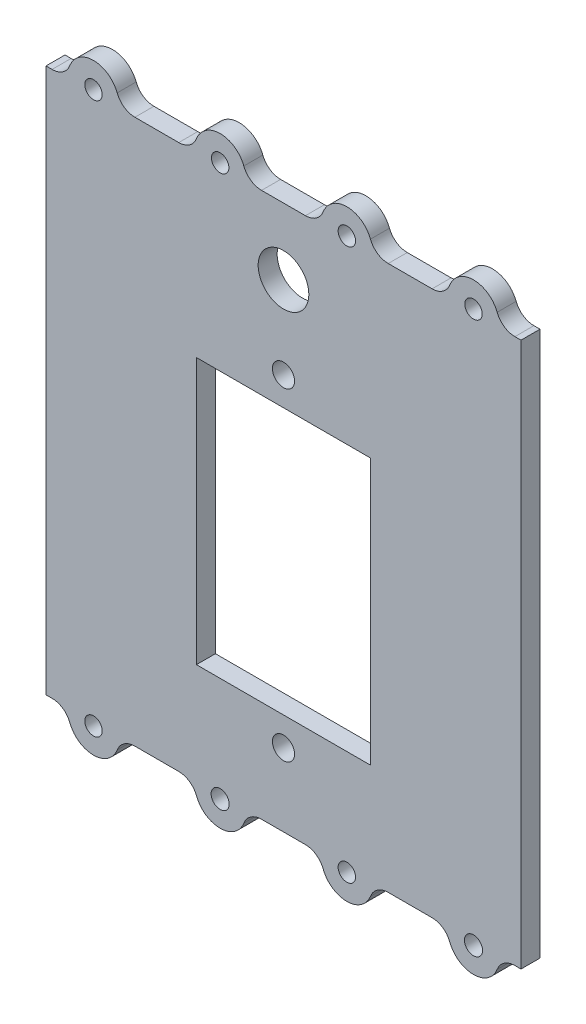
SolidWorks part; units mm, degrees
material "Aircraft Ply"
ref_plane "Front Plane" through (0, 0, 0) normal (0, 0, 1) x (1, 0, 0)
ref_plane "Top Plane" through (0, 0, 0) normal (0, 1, 0) x (1, 0, 0)
ref_plane "Right Plane" through (0, 0, 0) normal (1, 0, 0) x (0, 0, -1)
sketch "Sketch1" plane through (0, 0, 0) normal (0, 0, 1) x (1, 0, 0)
  line L13 (-3.4617, -43) -> (3.4617, -43)
  line L14 (16.5383, -43) -> (23.4617, -43)
  line L15 (36.5383, -43) -> (37.5, -43)
  line L16 (37.5, -43) -> (37.5, 43)
  line L17 (37.5, 43) -> (36.5383, 43)
  line L18 (23.4617, 43) -> (16.5383, 43)
  line L19 (3.4617, 43) -> (-3.4617, 43)
  line L20 (-16.5383, 43) -> (-23.4617, 43)
  line L21 (-36.5383, 43) -> (-37.5, 43)
  line L22 (-37.5, 43) -> (-37.5, -43)
  line L23 (-37.5, -43) -> (-36.5383, -43)
  line L24 (-23.4617, -43) -> (-16.5383, -43)
  line L25 (-3.4617, -43) -> (3.4617, -43)
  line L26 (16.5383, -43) -> (23.4617, -43)
  line L27 (36.5383, -43) -> (37.5, -43)
  line L28 (37.5, -43) -> (37.5, 43)
  line L29 (37.5, 43) -> (36.5383, 43)
  line L30 (23.4617, 43) -> (16.5383, 43)
  line L31 (3.4617, 43) -> (-3.4617, 43)
  line L32 (-16.5383, 43) -> (-23.4617, 43)
  line L33 (-36.5383, 43) -> (-37.5, 43)
  line L34 (-37.5, 43) -> (-37.5, -43)
  line L35 (-37.5, -43) -> (-36.5383, -43)
  line L36 (-23.4617, -43) -> (-16.5383, -43)
  circle A0 centre (-30, 43.5) radius 1.375
  circle A1 centre (-10, 43.5) radius 1.375
  circle A2 centre (10, 43.5) radius 1.375
  circle A3 centre (30, 43.5) radius 1.375
  circle A4 centre (-30, -43.5) radius 1.375
  circle A5 centre (-10, -43.5) radius 1.4286
  circle A6 centre (10, -43.5) radius 1.375
  circle A7 centre (30, -43.5) radius 1.4286
  arc A24 (-13.7362, -44.9286) -> (-6.2638, -44.9286) centre (-10, -43.5) ccw
  arc A25 (-3.4617, -43) -> (-6.2638, -44.9286) centre (-3.4617, -46) ccw
  arc A26 (6.2638, -44.9286) -> (3.4617, -43) centre (3.4617, -46) ccw
  arc A27 (6.2638, -44.9286) -> (13.7362, -44.9286) centre (10, -43.5) ccw
  arc A28 (16.5383, -43) -> (13.7362, -44.9286) centre (16.5383, -46) ccw
  arc A29 (26.2638, -44.9286) -> (23.4617, -43) centre (23.4617, -46) ccw
  arc A30 (26.2638, -44.9286) -> (33.7362, -44.9286) centre (30, -43.5) ccw
  arc A31 (36.5383, -43) -> (33.7362, -44.9286) centre (36.5383, -46) ccw
  arc A32 (33.7362, 44.9286) -> (36.5383, 43) centre (36.5383, 46) ccw
  arc A33 (33.7362, 44.9286) -> (26.2638, 44.9286) centre (30, 43.5) ccw
  arc A34 (23.4617, 43) -> (26.2638, 44.9286) centre (23.4617, 46) ccw
  arc A35 (13.7362, 44.9286) -> (16.5383, 43) centre (16.5383, 46) ccw
  arc A36 (13.7362, 44.9286) -> (6.2638, 44.9286) centre (10, 43.5) ccw
  arc A37 (3.4617, 43) -> (6.2638, 44.9286) centre (3.4617, 46) ccw
  arc A38 (-6.2638, 44.9286) -> (-3.4617, 43) centre (-3.4617, 46) ccw
  arc A39 (-6.2638, 44.9286) -> (-13.7362, 44.9286) centre (-10, 43.5) ccw
  arc A40 (-16.5383, 43) -> (-13.7362, 44.9286) centre (-16.5383, 46) ccw
  arc A41 (-26.2638, 44.9286) -> (-23.4617, 43) centre (-23.4617, 46) ccw
  arc A42 (-26.2638, 44.9286) -> (-33.7362, 44.9286) centre (-30, 43.5) ccw
  arc A43 (-36.5383, 43) -> (-33.7362, 44.9286) centre (-36.5383, 46) ccw
  arc A44 (-33.7362, -44.9286) -> (-36.5383, -43) centre (-36.5383, -46) ccw
  arc A45 (-33.7362, -44.9286) -> (-26.2638, -44.9286) centre (-30, -43.5) ccw
  arc A46 (-23.4617, -43) -> (-26.2638, -44.9286) centre (-23.4617, -46) ccw
  arc A47 (-13.7362, -44.9286) -> (-16.5383, -43) centre (-16.5383, -46) ccw
  arc A48 (-13.7362, -44.9286) -> (-6.2638, -44.9286) centre (-10, -43.5) ccw
  arc A49 (-3.4617, -43) -> (-6.2638, -44.9286) centre (-3.4617, -46) ccw
  arc A50 (6.2638, -44.9286) -> (3.4617, -43) centre (3.4617, -46) ccw
  arc A51 (6.2638, -44.9286) -> (13.7362, -44.9286) centre (10, -43.5) ccw
  arc A52 (16.5383, -43) -> (13.7362, -44.9286) centre (16.5383, -46) ccw
  arc A53 (26.2638, -44.9286) -> (23.4617, -43) centre (23.4617, -46) ccw
  arc A54 (26.2638, -44.9286) -> (33.7362, -44.9286) centre (30, -43.5) ccw
  arc A55 (36.5383, -43) -> (33.7362, -44.9286) centre (36.5383, -46) ccw
  arc A56 (33.7362, 44.9286) -> (36.5383, 43) centre (36.5383, 46) ccw
  arc A57 (33.7362, 44.9286) -> (26.2638, 44.9286) centre (30, 43.5) ccw
  arc A58 (23.4617, 43) -> (26.2638, 44.9286) centre (23.4617, 46) ccw
  arc A59 (13.7362, 44.9286) -> (16.5383, 43) centre (16.5383, 46) ccw
  arc A60 (13.7362, 44.9286) -> (6.2638, 44.9286) centre (10, 43.5) ccw
  arc A61 (3.4617, 43) -> (6.2638, 44.9286) centre (3.4617, 46) ccw
  arc A62 (-6.2638, 44.9286) -> (-3.4617, 43) centre (-3.4617, 46) ccw
  arc A63 (-6.2638, 44.9286) -> (-13.7362, 44.9286) centre (-10, 43.5) ccw
  arc A64 (-16.5383, 43) -> (-13.7362, 44.9286) centre (-16.5383, 46) ccw
  arc A65 (-26.2638, 44.9286) -> (-23.4617, 43) centre (-23.4617, 46) ccw
  arc A66 (-26.2638, 44.9286) -> (-33.7362, 44.9286) centre (-30, 43.5) ccw
  arc A67 (-36.5383, 43) -> (-33.7362, 44.9286) centre (-36.5383, 46) ccw
  arc A68 (-33.7362, -44.9286) -> (-36.5383, -43) centre (-36.5383, -46) ccw
  arc A69 (-33.7362, -44.9286) -> (-26.2638, -44.9286) centre (-30, -43.5) ccw
  arc A70 (-23.4617, -43) -> (-26.2638, -44.9286) centre (-23.4617, -46) ccw
  arc A71 (-13.7362, -44.9286) -> (-16.5383, -43) centre (-16.5383, -46) ccw
  dimension "D1" = 0
extrude "Boss-Extrude1" add sketch "Sketch1" along normal blind 3
sketch "Sketch2" plane through (0, 0, 0) normal (0, 0, 1) x (1, 0, 0)
  line L0 (0, 0) -> (0, 32.5) construction
  line L1 (0, 0) -> (0, -43) construction
  line L2 (-3.4617, -43) -> (3.4617, -43) construction
  line L4 (-13.75, 15) -> (13.75, 15)
  line L5 (-13.75, 15) -> (-13.75, -27)
  line L6 (-13.75, -27) -> (13.75, -27)
  line L7 (13.75, 15) -> (13.75, -27)
  line L8 (-13.75, 15) -> (13.75, -27) construction
  line L9 (-13.75, -27) -> (13.75, 15) construction
  circle A0 centre (0, 32.5) radius 4
  circle A1 centre (0, 19.5) radius 1.75
  circle A2 centre (0, -31.5) radius 1.75
  point P4 (0, -6)
  dimension "D1" = 8
  dimension "D8" = 3.5
  dimension "D2" = 32.5
  dimension "D3" = 42
  dimension "D4" = 27.5
  dimension "D5" = 6
  dimension "D6" = 4.5
  dimension "D7" = 4.5
extrude "Cut-Extrude1" cut sketch "Sketch2" along normal through all
